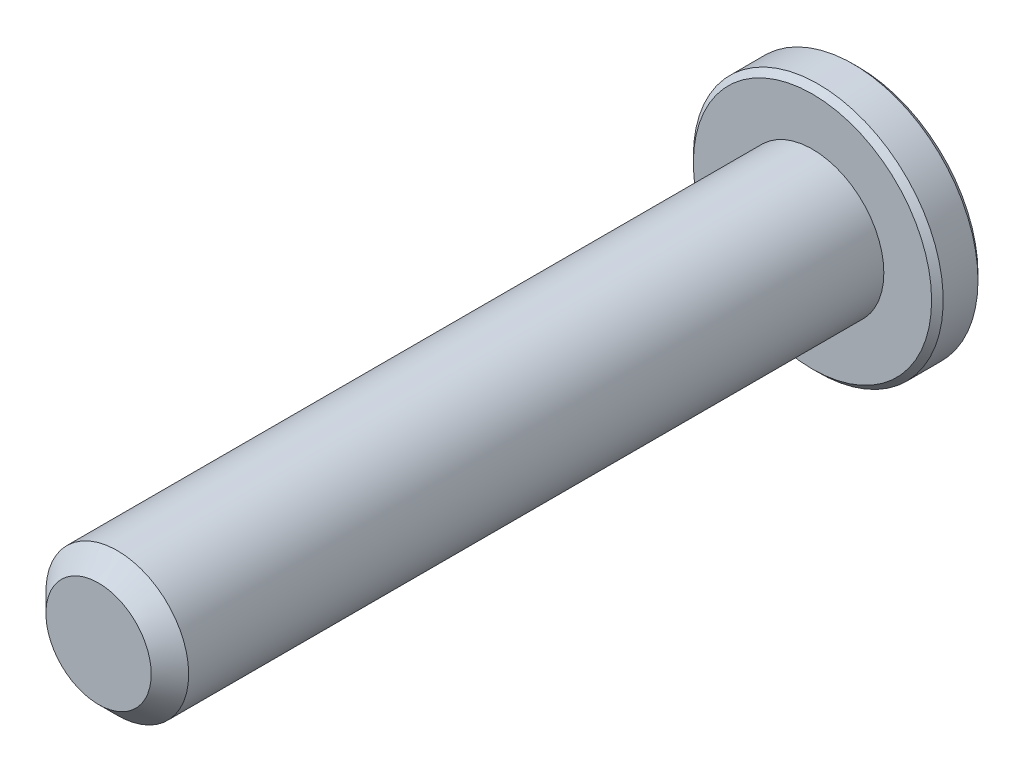
SolidWorks part; units mm, degrees
other "DetailItem1"
ref_plane "Front Plane" through (0, 0, 0) normal (0, 0, 1) x (1, 0, 0)
ref_plane "Top Plane" through (0, 0, 0) normal (0, 1, 0) x (1, 0, 0)
ref_plane "Right Plane" through (0, 0, 0) normal (1, 0, 0) x (0, 0, -1)
sketch "Sketch0" plane through (0, 0, 0) normal (1, 0, 0) x (0, 0, -1)
  line L0 (10.65, 0) -> (-10.65, 0) construction
  line L1 (10.65, 3.5) -> (10.65, -3.5) construction
  line L2 (10.65, 3.5) -> (9.35, 3.5) construction
  line L3 (-10.65, 0) -> (-10.65, 2) construction
  line L4 (-10.65, 2) -> (-9.95, 2) construction
  point P3 (10.65, 1.25)
  point P6 (10.65, 0)
  dimension "Head Diameter" = 7
  dimension "Drive Size" = 2.5
  dimension "Head Height" = 1.3
  dimension "Thread Pitch" = 0.7
  dimension "Thread Size" = 4
  dimension "Length" = 20
sketch "Sketch1" plane through (0, 0, 0) normal (0, 0, 1) x (1, 0, 0)
  circle A0 centre (0, 0) radius 2
extrude "Extrude1" add sketch "Sketch1" along normal up to vertex (10.65 mm away) from vertex up to point (0, 0, 10.65) starting at point (0, 3.5, -9.35)
sketch "Sketch6" plane through (0, 0, 0) normal (0, 0, 1) x (1, 0, 0)
  circle A0 centre (0, 0) radius 3.5
extrude "Extrude2" add sketch "Sketch6" along normal up to vertex (-9.35 mm away) from vertex up to point (0, 3.5, -9.35) starting at point (0, 3.5, -10.65)
sketch "Sketch7" plane through (0, 0, -10.65) normal (0, 0, 1) x (1, 0, 0)
  line L1 (0, 1.4434) -> (-1.25, 0.7217)
  line L2 (-1.25, 0.7217) -> (-1.25, -0.7217)
  line L3 (-1.25, -0.7217) -> (0, -1.4434)
  line L4 (0, -1.4434) -> (1.25, -0.7217)
  line L5 (1.25, -0.7217) -> (1.25, 0.7217)
  line L6 (1.25, 0.7217) -> (0, 1.4434)
  circle A0 centre (0, 0) radius 1.25 construction
extrude "Cut-Extrude1" cut sketch "Sketch7" along normal blind 0.975
sketch "Sketch8" plane through (0, 0, -10.65) normal (0, 0, 1) x (1, 0, 0)
  circle A0 centre (0, 0) radius 1.4434
extrude "Cut-Extrude2" cut sketch "Sketch8" along normal up to next (0.975 mm away) draft 45
chamfer "Chamfer1" distance 0.1625 angle 45 2 edges at (3.5, 0, -9.35) (3.5, 0, -10.65)
chamfer "Chamfer2" distance 0.525 angle 45 1 edges at (2, 0, 10.65)
split "Split1" [suppressed] bodies to split 107
sketch "Sketch2" [suppressed] plane through (0, 0, 10.65) normal (0, 0, -1) x (-1, 0, 0)
  circle A1 centre (0, 0) radius 2
curve "Helix/Spiral1" [suppressed] pitch 0.7 height 20.7 turns 29.5714 parameters "pitch"=0.7
sketch "Sketch3" [suppressed] plane through (0, 0, 0) normal (1, 0, 0) x (0, 0, -1)
  line L0 (-11.3063, 2.0758) -> (-10.9563, 1.4696) construction
  line L1 (-10.9563, 1.4696) -> (-10.6063, 2.0758) construction
  line L2 (-10.6063, 2.0758) -> (-11.3063, 2.0758) construction
  line L3 (-11.2625, 2) -> (-10.65, 2) construction
  line L4 (-10.9563, 2.0758) -> (-10.9563, 2) construction
  line L5 (-10.9563, 2) -> (-10.9563, 1.5453) construction
  line L6 (-10.9563, 1.5453) -> (-10.9563, 1.4696) construction
  line L7 (-11, 1.5453) -> (-10.9125, 1.5453)
  line L8 (-11.2844, 2.0379) -> (-10.6281, 2.0379)
  line L9 (-10.9125, 1.5453) -> (-10.6281, 2.0379)
  line L10 (-11, 1.5453) -> (-11.2844, 2.0379)
  line L12 (-10.65, 0) -> (-10.65, 2) construction
  line L13 (-10.125, -2) -> (9.35, -2) construction
  point P14 (-10.9563, 2.0379)
  point P17 (-8.9, -2)
  dimension "D1" = 0.7
  dimension "D2" = 0.0875
  dimension "D3" = 1.75
sweep "Cut-Sweep1" [suppressed] cut profiles "Sketch3" path "Helix/Spiral1"
sketch "Sketch9" [suppressed] plane through (0, 0, 0) normal (1, 0, 0) x (0, 0, -1)
  line L0 (9.35, 2) -> (8.3086, 2)
  line L1 (9.35, 3.3375) -> (9.35, -3.3375) construction
  line L2 (8.3086, 2) -> (7.7782, 1.4696)
  line L3 (7.7782, 1.4696) -> (7.7782, 0)
  line L4 (10.65, 0) -> (-10.65, 0) construction
  line L5 (7.7782, 0) -> (9.35, 0)
  line L6 (9.35, 0) -> (9.35, 2)
  dimension "D1" = 45
  dimension "Relief" = 1.0414
revolve "Revolve1" [suppressed] add sketch "Sketch9" angle 360 about L0
equation "\"D3@Helix/Spiral1\" = \"Length@Sketch0\" + \"Thread Pitch@Sketch0\""
equation "\"D1@Cut-Extrude1\"=\"Head Height@Sketch0\"*.75"
equation "\"D1@Chamfer1\" = \"Head Height@Sketch0\" * 0.125"
equation "\"pitch@Helix/Spiral1\" = \"Thread Pitch@Sketch0\""
equation "\"D2@Sketch3\"=\"D1@Sketch3\"/8"
equation "\"D1@Sketch3\" = \"Thread Pitch@Sketch0\""
equation "\"D3@Sketch3\" = \"Thread Pitch@Sketch0\" * 2.5"
equation "\"D1@Chamfer2\"=\"thread pitch@sketch0\"*0.75"
